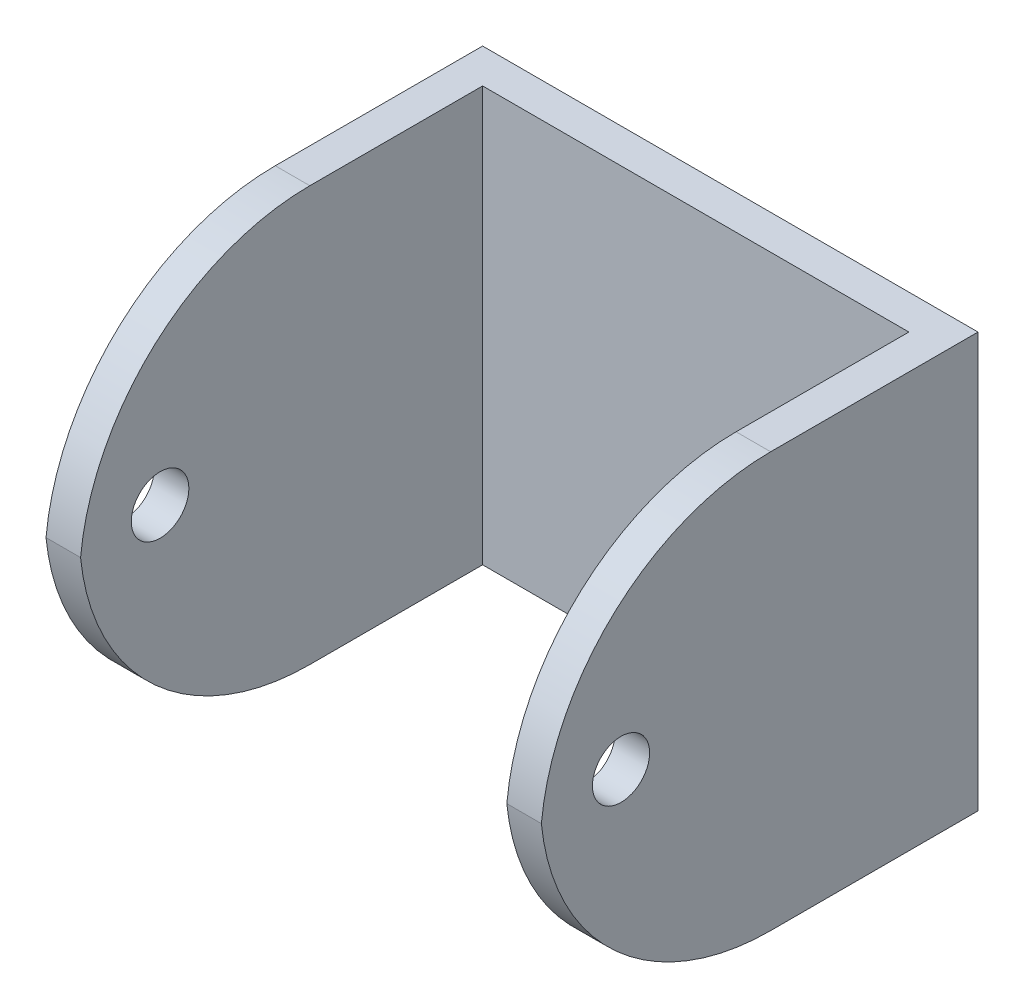
SolidWorks part; units mm, degrees
ref_plane "Plan de face" through (0, 0, 0) normal (0, 0, 1) x (1, 0, 0)
ref_plane "Plan de dessus" through (0, 0, 0) normal (0, 1, 0) x (1, 0, 0)
ref_plane "Plan de droite" through (0, 0, 0) normal (1, 0, 0) x (0, 0, -1)
sketch "Esquisse1" plane through (0, 0, 0) normal (0, 0, 1) x (1, 0, 0)
  line L1 (-74.0142, 31.5996) -> (-31.0142, 31.5996)
  line L2 (-74.0142, 31.5996) -> (-74.0142, -4.4004)
  line L3 (-74.0142, -4.4004) -> (-31.0142, -4.4004)
  line L4 (-31.0142, 31.5996) -> (-31.0142, -4.4004)
  dimension "D1" = 43
  dimension "D2" = 36
extrude "Boss.-Extru.1" add sketch "Esquisse1" along normal blind 3
sketch "Esquisse2" plane through (0, 0, 3) normal (0, 0, 1) x (1, 0, 0)
  line L0 (-74.0142, -4.4004) -> (-31.0142, -4.4004) construction
  line L1 (-31.0142, 31.5996) -> (-34.0142, 31.5996)
  line L2 (-31.0142, 31.5996) -> (-31.0142, -4.4004)
  line L3 (-31.0142, -4.4004) -> (-34.0142, -4.4004)
  line L4 (-34.0142, 31.5996) -> (-34.0142, -4.4004)
  dimension "D1" = 3
extrude "Boss.-Extru.2" add sketch "Esquisse2" along normal blind 25
sketch "Esquisse3" plane through (0, 0, 3) normal (0, 0, 1) x (1, 0, 0)
  line L0 (-74.0142, -4.4004) -> (-34.0142, -4.4004) construction
  line L1 (-74.0142, 31.5996) -> (-71.0142, 31.5996)
  line L2 (-74.0142, 31.5996) -> (-74.0142, -4.4004)
  line L3 (-74.0142, -4.4004) -> (-71.0142, -4.4004)
  line L4 (-71.0142, 31.5996) -> (-71.0142, -4.4004)
  dimension "D1" = 3
extrude "Boss.-Extru.3" add sketch "Esquisse3" along normal blind 35
sketch "Esquisse4" plane through (-74.0142, 0, 0) normal (-1, 0, 0) x (0, 0, 1)
  line L0 (38, 31.5996) -> (0, 31.5996) construction
  line L1 (38, 31.5996) -> (38, -4.4004) construction
  circle A0 centre (31, 14.0996) radius 2.5
  dimension "D1" = 5
  dimension "D2" = 17.5
  dimension "D3" = 7
extrude "Enlèv. mat.-Extru.1" cut sketch "Esquisse4" against normal blind 95
fillet "Congé1" radius 20 4 edges at (-32.5142, -4.4004, 28) (-32.5142, 31.5996, 28) (-72.5142, -4.4004, 38) (-72.5142, 31.5996, 38)
sketch "Esquisse5" plane through (-34.0142, 0, 0) normal (-1, 0, 0) x (0, 0, 1)
  line L1 (3, 31.5996) -> (49.07, 31.5996)
  line L2 (3, 31.5996) -> (3, -11.9999)
  line L3 (3, -11.9999) -> (49.07, -11.9999)
  line L4 (49.07, 31.5996) -> (49.07, -11.9999)
extrude "Enlèv. mat.-Extru.2" cut sketch "Esquisse5" against normal blind 95
sketch "Esquisse6" plane through (0, 0, 3) normal (0, 0, 1) x (1, 0, 0)
  line L0 (-71.0142, -4.4004) -> (-31.0142, -4.4004) construction
  line L1 (-31.0142, 31.5996) -> (-34.0142, 31.5996)
  line L2 (-31.0142, 31.5996) -> (-31.0142, -4.4004)
  line L3 (-31.0142, -4.4004) -> (-34.0142, -4.4004)
  line L4 (-34.0142, 31.5996) -> (-34.0142, -4.4004)
  dimension "D1" = 3
extrude "Boss.-Extru.4" add sketch "Esquisse6" along normal blind 35
sketch "Esquisse7" plane through (-34.0142, 0, 0) normal (-1, 0, 0) x (0, 0, 1)
  circle A0 centre (30.9859, 14.217) radius 2.4826
extrude "Enlèv. mat.-Extru.3" cut sketch "Esquisse7" against normal blind 35
fillet "Congé2" radius 20 2 edges at (-32.5142, -4.4004, 38) (-32.5142, 31.5996, 38)
